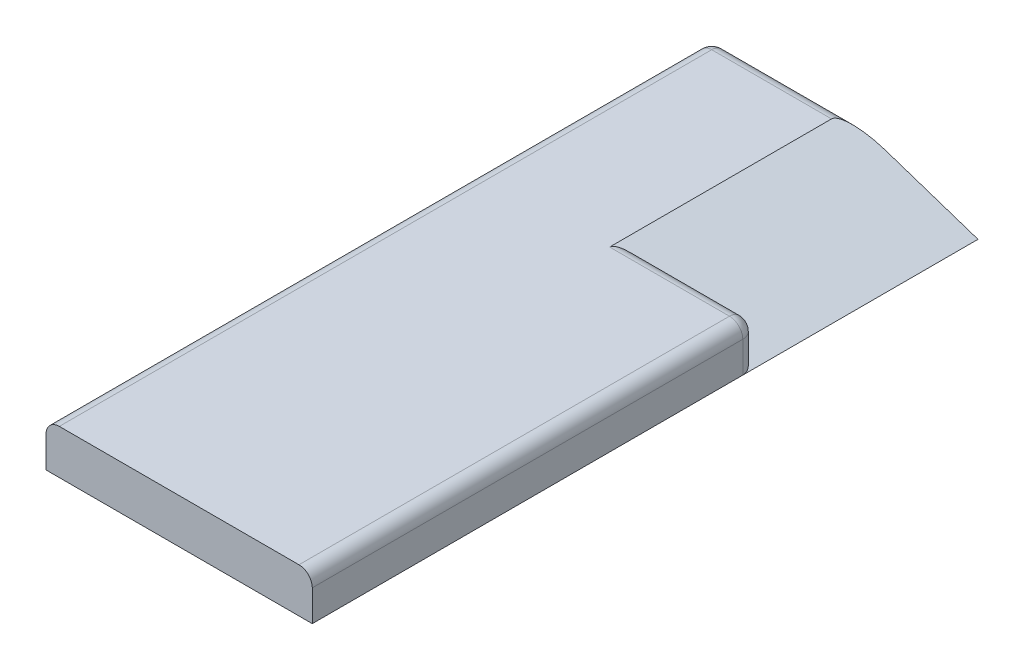
SolidWorks part; units mm, degrees
ref_plane "Front Plane" through (0, 0, 0) normal (0, 0, 1) x (1, 0, 0)
ref_plane "Top Plane" through (0, 0, 0) normal (0, 1, 0) x (1, 0, 0)
ref_plane "Right Plane" through (0, 0, 0) normal (1, 0, 0) x (0, 0, -1)
sketch "Sketch1" plane through (0, 0, 0) normal (0, 0, 1) x (1, 0, 0)
  line L1 (-30, 5) -> (30, 5)
  line L2 (-30, 5) -> (-30, -5)
  line L3 (-30, -5) -> (30, -5)
  line L4 (30, 5) -> (30, -5)
  line L5 (-30, 5) -> (30, -5) construction
  line L6 (-30, -5) -> (30, 5) construction
  point P0 (0, 0)
  dimension "D1" = 60
  dimension "D2" = 10
extrude "Boss-Extrude1" add sketch "Sketch1" along normal blind 150 contours L2 L3 L4 L1
sketch "Sketch2" plane through (0, 0, 0) normal (0, 0, -1) x (-1, 0, 0)
  line L0 (30, -5) -> (-30, -5)
  line L1 (-30, -5) -> (0, 5)
  line L2 (30, 5) -> (-30, 5) construction
  line L3 (0, 5) -> (30, 5)
  line L4 (30, 5) -> (30, -5)
  line L5 (0, 5) -> (-30, 5)
  line L6 (-30, 5) -> (-30, -5)
extrude "Cut-Extrude3" cut sketch "Sketch2" against normal blind 50 and the other way through all contours L1
fillet "Fillet5" radius 3 3 edges at (30, 0, 50) (15, 5, 50) (-15, 5, 0)
fillet "Fillet6" radius 3 3 edges at (-30, -1.5, 0) (-30, 4.1213, 0.8787) (-30, 5, 76.5)
fillet "Fillet7" radius 3 2 edges at (29.1213, 4.1213, 50.8787) (30, 5, 101.5)
